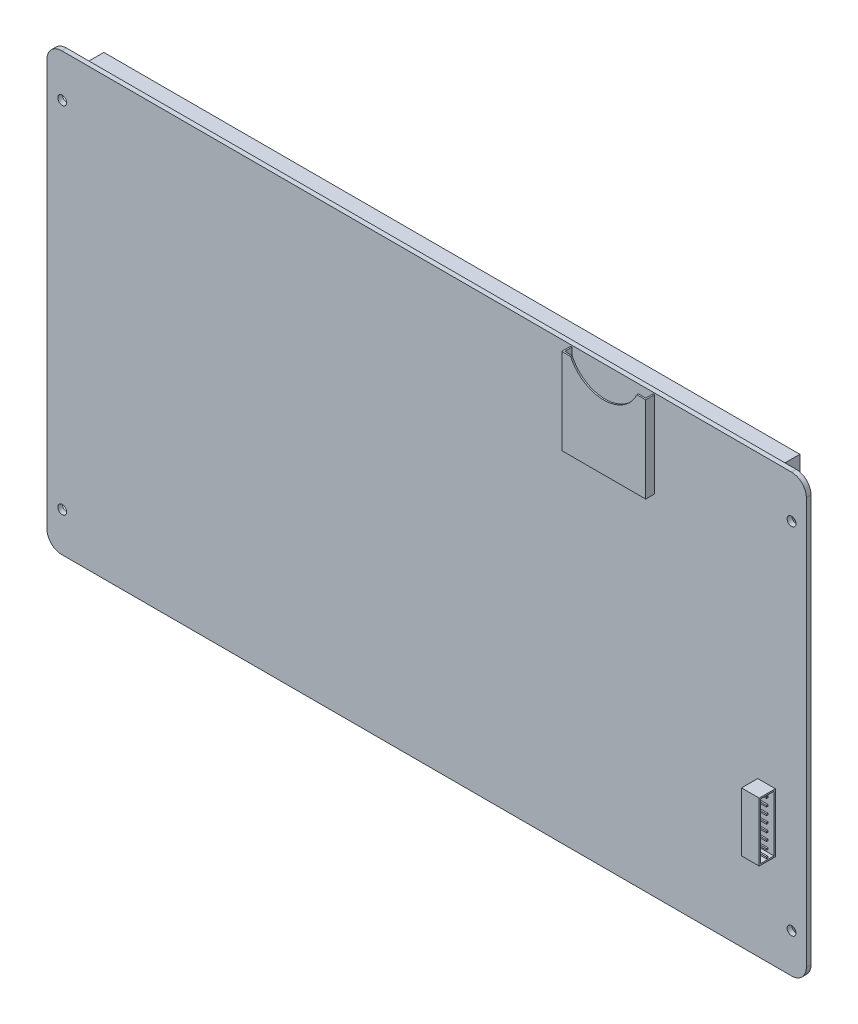
SolidWorks part; units mm, degrees
ref_plane "前视基准面" through (0, 0, 0) normal (0, 0, 1) x (1, 0, 0)
ref_plane "上视基准面" through (0, 0, 0) normal (0, 1, 0) x (1, 0, 0)
ref_plane "右视基准面" through (0, 0, 0) normal (1, 0, 0) x (0, 0, -1)
sketch "草图1" plane through (0, 0, 0) normal (0, 0, 1) x (1, 0, 0)
  line L0 (-144.5066, 0) -> (161.1709, 0) construction
  line L1 (-128.95, 74.1) -> (128.95, 74.1)
  line L2 (-128.95, 74.1) -> (-128.95, -74.1)
  line L3 (-128.95, -74.1) -> (128.95, -74.1)
  line L4 (128.95, 74.1) -> (128.95, -74.1)
  line L5 (0, 107.2959) -> (0, -142.0898) construction
  dimension "D1" = 257.9
  dimension "D2" = 148.2
extrude "凸台-拉伸1" add sketch "草图1" along normal blind 1.6
fillet "圆角1" radius 5 4 edges at (-128.95, 74.1, 0.8) (128.95, 74.1, 0.8) (128.95, -74.1, 0.8) (-128.95, -74.1, 0.8)
sketch "草图2" plane through (0, 0, 0) normal (0, 0, 1) x (1, 0, 0)
  line L0 (-164.9706, -0.57) -> (171.4976, -0.57) construction
  line L1 (0.08, 100.0267) -> (0.08, -104.2693) construction
  line L2 (128.95, -69.1) -> (128.95, 69.1) construction
  line L3 (123.95, 74.1) -> (-123.95, 74.1) construction
  circle A0 centre (-123.77, 59.63) radius 1.5
  circle A1 centre (123.93, 59.63) radius 1.5
  circle A2 centre (123.93, -60.77) radius 1.5
  circle A3 centre (-123.77, -60.77) radius 1.5
  dimension "D1" = 3
  dimension "D2" = 120.4
  dimension "D3" = 247.7
  dimension "D4" = 5.02
  dimension "D5" = 14.47
extrude "固定孔" cut sketch "草图2" along normal blind 1.6
sketch "草图3" plane through (0, 0, 0) normal (0, 0, -1) x (-1, 0, 0)
  line L0 (-152.5693, 0.07) -> (159.4226, 0.07) construction
  line L1 (-118.27, 72.27) -> (118.13, 72.27)
  line L2 (-118.27, 72.27) -> (-118.27, -72.13)
  line L3 (-118.27, -72.13) -> (118.13, -72.13)
  line L4 (118.13, 72.27) -> (118.13, -72.13)
  line L5 (-0.07, 91.2152) -> (-0.07, -110.4699) construction
  circle A0 centre (-123.93, 59.63) radius 1.5 construction
  dimension "D3" = 5.66
  dimension "D1" = 236.4
  dimension "D2" = 144.4
  dimension "D4" = 12.64
extrude "液晶压片厚" add sketch "草图3" along normal blind 6.4
sketch "草图4" plane through (0, 0, -6.4) normal (0, 0, -1) x (-1, 0, 0)
  line L0 (-158.1172, -0.02) -> (155.5064, -0.02) construction
  line L1 (-114.03, 63.88) -> (111.87, 63.88)
  line L2 (-114.03, 63.88) -> (-114.03, -63.92)
  line L3 (-114.03, -63.92) -> (111.87, -63.92)
  line L4 (111.87, 63.88) -> (111.87, -63.92)
  line L5 (-1.08, 89.9098) -> (-1.08, -103.9429) construction
  line L6 (-118.27, -72.13) -> (118.13, -72.13) construction
  line L7 (-118.27, 72.27) -> (-118.27, -72.13) construction
  line L8 (118.13, 72.27) -> (-118.27, 72.27) construction
  line L9 (118.13, -72.13) -> (118.13, 72.27) construction
  line L10 (-118.27, -72.13) -> (118.13, -72.13)
  line L11 (-118.27, 72.27) -> (-118.27, -72.13)
  line L12 (118.13, 72.27) -> (-118.27, 72.27)
  line L13 (118.13, -72.13) -> (118.13, 72.27)
  circle A0 centre (-123.93, 59.63) radius 1.5 construction
  dimension "D1" = 225.9
  dimension "D2" = 127.8
  dimension "D3" = 4.25
  dimension "D4" = 9.9
extrude "铁框架" add sketch "草图4" along normal blind 0.5
sketch "草图5" plane through (0, 0, -6.4) normal (0, 0, -1) x (-1, 0, 0)
  line L0 (-1.08, 106.0487) -> (-1.08, -119.9355) construction
  line L1 (-112.43, 62.63) -> (110.27, 62.63)
  line L2 (-112.43, 62.63) -> (-112.43, -62.67)
  line L3 (-112.43, -62.67) -> (110.27, -62.67)
  line L4 (110.27, 62.63) -> (110.27, -62.67)
  line L5 (-179.6686, -0.02) -> (149.5044, -0.02) construction
  circle A1 centre (-123.93, 59.63) radius 1.5 construction
  dimension "D4" = 3
  dimension "D3" = 11.5
  dimension "D1" = 222.7
  dimension "D2" = 125.3
extrude "显示区域" add sketch "草图5" along normal blind 0.5
sketch "草图6" plane through (0, 0, -6.4) normal (0, 0, -1) x (-1, 0, 0)
  line L0 (111.87, 63.88) -> (-114.03, 63.88) construction
  line L1 (110.27, 62.63) -> (-112.43, 62.63) construction
  line L2 (-114.03, 63.88) -> (-114.03, -63.92) construction
  line L3 (-112.43, 62.63) -> (-112.43, -62.67) construction
  line L4 (-114.03, -63.92) -> (111.87, -63.92) construction
  line L5 (-112.43, -62.67) -> (110.27, -62.67) construction
  line L6 (111.87, -63.92) -> (111.87, 63.88) construction
  line L7 (110.27, -62.67) -> (110.27, 62.63) construction
  line L8 (111.87, 63.88) -> (-114.03, 63.88)
  line L9 (110.27, 62.63) -> (-112.43, 62.63)
  line L10 (-114.03, 63.88) -> (-114.03, -63.92)
  line L11 (-112.43, 62.63) -> (-112.43, -62.67)
  line L12 (-114.03, -63.92) -> (111.87, -63.92)
  line L13 (-112.43, -62.67) -> (110.27, -62.67)
  line L14 (111.87, -63.92) -> (111.87, 63.88)
  line L15 (110.27, -62.67) -> (110.27, 62.63)
extrude "显示过渡区" add sketch "草图6" along normal blind 0.4
ref_plane "显示中心x_距原中心右偏移0.05" through (1.08, 0, 0) normal (1, 0, 0) x (0, 0, -1)
ref_plane "显示中心y-距原中心上偏称0.05" through (0, -0.02, 0) normal (0, 1, 0) x (1, 0, 0)
sketch "草图7" plane through (0, 0, 1.6) normal (0, 0, 1) x (1, 0, 0)
  line L0 (136.8543, -31.77) -> (52.6887, -31.77) construction
  line L1 (112.45, -21.77) -> (118.45, -21.77)
  line L2 (112.45, -21.77) -> (112.45, -41.77)
  line L3 (112.45, -41.77) -> (118.45, -41.77)
  line L4 (118.45, -21.77) -> (118.45, -41.77)
  line L5 (128.95, -69.1) -> (128.95, 69.1) construction
  circle A0 centre (123.93, 59.63) radius 1.5 construction
  circle A1 centre (123.93, -60.77) radius 1.5 construction
  dimension "D1" = 6
  dimension "D2" = 20
  dimension "D3" = 29
  dimension "D4" = 10.5
extrude "凸台-拉伸4" add sketch "草图7" along normal blind 5.5
sketch "草图8" plane through (118.45, 0, 0) normal (1, 0, 0) x (0, 0, -1)
  line L0 (-7.1, -41.77) -> (-7.1, -21.77) construction
  line L1 (-6.6, -22.27) -> (-2.1, -22.27)
  line L2 (-6.6, -22.27) -> (-6.6, -41.27)
  line L3 (-6.6, -41.27) -> (-2.1, -41.27)
  line L4 (-2.1, -22.27) -> (-2.1, -41.27)
  line L5 (-7.1, -21.77) -> (-1.6, -21.77) construction
  line L6 (-1.6, -69.1) -> (-1.6, 69.1) construction
  line L7 (-7.1, -41.77) -> (-1.6, -41.77) construction
  dimension "D1" = 0.5
  dimension "D2" = 0.5
  dimension "D3" = 0.5
  dimension "D4" = 0.5
extrude "切除-拉伸1" cut sketch "草图8" against normal blind 5
sketch "草图9" plane through (113.45, 0, 0) normal (1, 0, 0) x (0, 0, -1)
  line L0 (-4.35, 44.2351) -> (-4.35, 15.8893) construction
  line L1 (-9.9211, -31.77) -> (11.4481, -31.77) construction
  line L2 (-7.1, -21.77) -> (-1.6, -21.77) construction
  line L3 (-7.1, -41.77) -> (-1.6, -41.77) construction
  line L4 (-7.1, -41.77) -> (-7.1, -21.77) construction
  line L5 (-1.6, -41.77) -> (-1.6, -21.77) construction
  line L6 (-5.1262, -30.5) -> (-3.1287, -30.5) construction
  line L7 (-4.6, -30.25) -> (-4.1, -30.25)
  line L8 (-4.6, -30.25) -> (-4.6, -30.75)
  line L9 (-4.6, -30.75) -> (-4.1, -30.75)
  line L10 (-4.1, -30.25) -> (-4.1, -30.75)
  line L11 (-4.6, -27.71) -> (-4.1, -27.71)
  line L12 (-4.6, -27.71) -> (-4.6, -28.21)
  line L13 (-4.6, -28.21) -> (-4.1, -28.21)
  line L14 (-4.1, -27.71) -> (-4.1, -28.21)
  line L15 (-5.1262, -27.96) -> (-3.1287, -27.96) construction
  line L16 (-4.6, -25.17) -> (-4.1, -25.17)
  line L17 (-4.6, -25.17) -> (-4.6, -25.67)
  line L18 (-4.6, -25.67) -> (-4.1, -25.67)
  line L19 (-4.1, -25.17) -> (-4.1, -25.67)
  line L20 (-5.1262, -25.42) -> (-3.1287, -25.42) construction
  line L21 (-4.6, -22.63) -> (-4.1, -22.63)
  line L22 (-4.6, -22.63) -> (-4.6, -23.13)
  line L23 (-4.6, -23.13) -> (-4.1, -23.13)
  line L24 (-4.1, -22.63) -> (-4.1, -23.13)
  line L25 (-5.1262, -22.88) -> (-3.1287, -22.88) construction
  line L26 (-5.1262, -40.66) -> (-3.1287, -40.66) construction
  line L27 (-5.1262, -38.12) -> (-3.1287, -38.12) construction
  line L28 (-5.1262, -35.58) -> (-3.1287, -35.58) construction
  line L29 (-5.1262, -33.04) -> (-3.1287, -33.04) construction
  line L30 (-4.1, -40.91) -> (-4.1, -40.41)
  line L31 (-4.6, -40.41) -> (-4.1, -40.41)
  line L32 (-4.6, -40.91) -> (-4.6, -40.41)
  line L33 (-4.6, -40.91) -> (-4.1, -40.91)
  line L34 (-4.1, -38.37) -> (-4.1, -37.87)
  line L35 (-4.6, -37.87) -> (-4.1, -37.87)
  line L36 (-4.6, -38.37) -> (-4.6, -37.87)
  line L37 (-4.6, -38.37) -> (-4.1, -38.37)
  line L38 (-4.1, -35.83) -> (-4.1, -35.33)
  line L39 (-4.6, -35.33) -> (-4.1, -35.33)
  line L40 (-4.6, -35.83) -> (-4.6, -35.33)
  line L41 (-4.6, -35.83) -> (-4.1, -35.83)
  line L42 (-4.1, -33.29) -> (-4.1, -32.79)
  line L43 (-4.6, -32.79) -> (-4.1, -32.79)
  line L44 (-4.6, -33.29) -> (-4.6, -32.79)
  line L45 (-4.6, -33.29) -> (-4.1, -33.29)
  dimension "D2" = 2.54
  dimension "D3" = 0.5
  dimension "D4" = 0.5
  dimension "D1" = 4
extrude "凸台-拉伸5" add sketch "草图9" along normal blind 5
sketch "草图10" plane through (0, 0, 1.6) normal (0, 0, 1) x (1, 0, 0)
  line L0 (63.15, 19.8454) -> (63.15, 97.937) construction
  line L1 (128.95, -69.1) -> (128.95, 69.1) construction
  line L2 (51.9, 73.6) -> (48.9, 73.6)
  line L3 (34.8341, 66.4) -> (83.1127, 66.4) construction
  line L4 (48.9, 73.6) -> (48.9, 44.4)
  line L5 (48.9, 44.4) -> (77.4, 44.4)
  line L6 (77.4, 73.6) -> (77.4, 44.4)
  line L7 (74.4, 73.6) -> (77.4, 73.6)
  line L8 (123.95, 74.1) -> (-123.95, 74.1) construction
  arc A0 (51.9, 73.6) -> (74.4, 73.6) centre (63.15, 78.7891) ccw
  point P11 (63.15, 44.4)
  dimension "D6" = 7.2
  dimension "D1" = 65.8
  dimension "D2" = 28.5
  dimension "D3" = 22.5
  dimension "D4" = 0.5
  dimension "D5" = 29.2
extrude "凸台-拉伸6" add sketch "草图10" along normal blind 3
sketch "草图11" plane through (0, 73.6, 0) normal (0, 1, 0) x (1, 0, 0)
  line L0 (123.95, -1.6) -> (-123.95, -1.6) construction
  line L1 (49.4, -1.6) -> (76.9, -1.6)
  line L2 (49.4, -1.6) -> (49.4, -4.1)
  line L3 (49.4, -4.1) -> (76.9, -4.1)
  line L4 (76.9, -1.6) -> (76.9, -4.1)
  line L5 (77.4, -4.6) -> (74.4, -4.6) construction
  line L6 (77.4, -4.6) -> (77.4, -1.6) construction
  line L7 (48.9, -4.6) -> (48.9, -1.6) construction
  point P8 (77.4, -3.1)
  dimension "D1" = 0.5
  dimension "D2" = 0.5
  dimension "D3" = 0.5
extrude "切除-拉伸2" cut sketch "草图11" against normal blind 25
